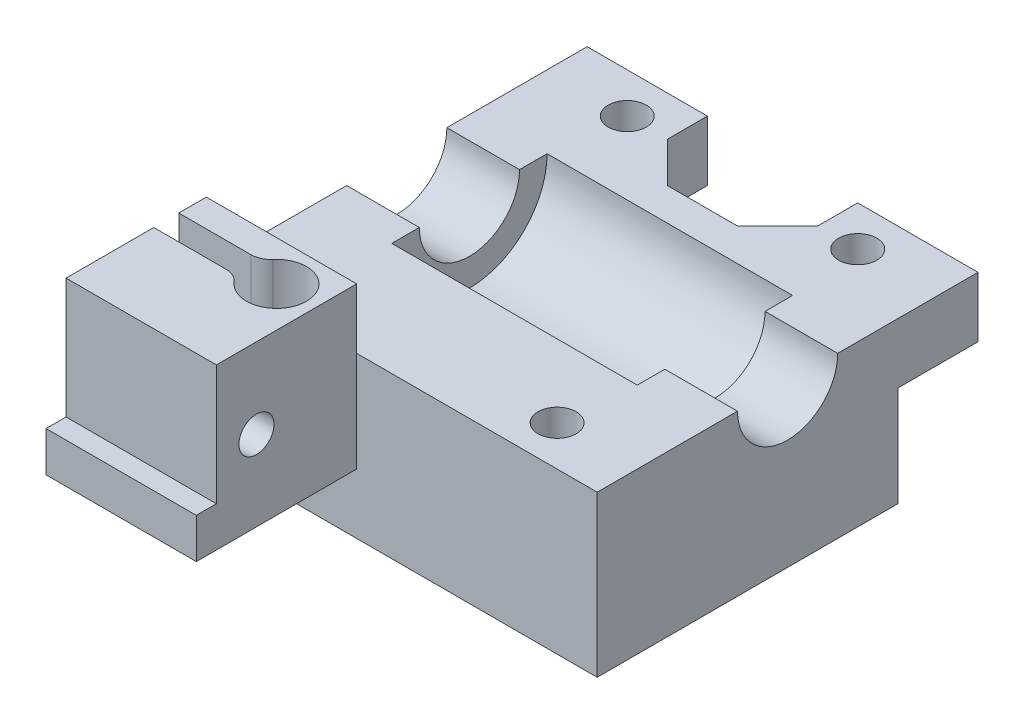
SolidWorks part; units mm, degrees
ref_plane "Front Plane" through (0, 0, 0) normal (0, 0, 1) x (1, 0, 0)
ref_plane "Top Plane" through (0, 0, 0) normal (0, 1, 0) x (1, 0, 0)
ref_plane "Right Plane" through (0, 0, 0) normal (1, 0, 0) x (0, 0, -1)
sketch "Sketch1" plane through (0, 0, 0) normal (0, 1, 0) x (1, 0, 0)
  line L1 (-15.5, 11) -> (15.5, 11)
  line L2 (-15.5, 11) -> (-15.5, -11)
  line L3 (-15.5, -11) -> (15.5, -11)
  line L4 (15.5, 11) -> (15.5, -11)
  line L5 (-15.5, 11) -> (15.5, -11) construction
  line L6 (-15.5, -11) -> (15.5, 11) construction
  point P0 (0, 0)
  dimension "D1" = 31
  dimension "D2" = 22
extrude "Boss-Extrude1" add sketch "Sketch1" along normal blind 11
sketch "Sketch2" plane through (0, 0, 0) normal (0, 1, 0) x (1, 0, 0)
  line L4 (15.5, -11) -> (15.5, 11)
  line L5 (-15.5, -11) -> (15.5, -11)
  line L6 (-15.5, 11) -> (-15.5, -11)
  line L7 (15.5, 11) -> (-15.5, 11)
  line L8 (15.5, -11) -> (15.5, 11)
  line L9 (-15.5, -11) -> (15.5, -11)
  line L10 (-15.5, 11) -> (-15.5, -11)
  line L11 (15.5, 11) -> (-15.5, 11)
  circle A0 centre (0, 0) radius 7.8438
  dimension "D1" = 0
extrude "Boss-Extrude2" add sketch "Sketch2" against normal blind 5
sketch "Sketch3" plane through (0, 11, 0) normal (0, 1, 0) x (1, 0, 0)
  line L1 (12.25, -7.75) -> (-12.25, -7.75)
  line L2 (12.25, -7.75) -> (12.25, 7.75)
  line L3 (12.25, 7.75) -> (-12.25, 7.75)
  line L4 (-12.25, -7.75) -> (-12.25, 7.75)
  line L5 (12.25, -7.75) -> (-12.25, 7.75) construction
  line L6 (12.25, 7.75) -> (-12.25, -7.75) construction
  point P0 (0, 0)
  dimension "D1" = 15.5
  dimension "D2" = 24.5
extrude "Cut-Extrude1" cut sketch "Sketch3" against normal blind 7.75
fillet "Fillet1" radius 7.75 2 edges at (0, 3.25, 7.75) (0, 3.25, -7.75)
sketch "Sketch4" plane through (-12.25, 0, 0) normal (1, 0, 0) x (0, 0, -1)
  line L0 (7.75, 11) -> (-7.75, 11) construction
  circle A0 centre (0, 11) radius 5
  dimension "D1" = 10
extrude "Cut-Extrude2" cut sketch "Sketch4" against normal through all both and the other way through all
sketch "Sketch5" plane through (0, 11, 0) normal (0, 1, 0) x (1, 0, 0)
  line L1 (15.5, -11) -> (7.5, -11)
  line L2 (15.5, -11) -> (15.5, -19)
  line L3 (15.5, -19) -> (7.5, -19)
  line L4 (7.5, -11) -> (7.5, -19)
  circle A0 centre (11.5, -15) radius 1.9058
  dimension "D1" = 8
  dimension "D2" = 8
  dimension "D3" = 4
  dimension "D4" = 4
extrude "Boss-Extrude3" add sketch "Sketch5" against normal blind 6
sketch "Sketch6" plane through (0, 5, 0) normal (0, -1, 0) x (1, 0, 0)
  line L4 (15.5, 11) -> (15.5, 19)
  line L5 (15.5, 19) -> (7.5, 19)
  line L6 (7.5, 19) -> (7.5, 11)
  line L7 (7.5, 11) -> (15.5, 11)
  line L8 (15.5, 11) -> (15.5, 19)
  line L9 (15.5, 19) -> (7.5, 19)
  line L10 (7.5, 19) -> (7.5, 11)
  line L11 (7.5, 11) -> (15.5, 11)
  circle A0 centre (11.5, 15) radius 1.9058 construction
  circle A1 centre (11.5, 15) radius 1.9058
  circle A2 centre (11.5, 15) radius 3
  circle M6 centre (11.5, 15) radius 1.9058
  dimension "D2" = 6
  dimension "D1" = 0
extrude "Cut-Extrude3" cut sketch "Sketch6" against normal blind 3 contours A2 M6 region at (8.5849, 5, 15)
mirror "Mirror8" about plane through (0, 0, 0) normal (1, 0, 0) of "Cut-Extrude3", "Boss-Extrude3"
mirror "Mirror9" about plane through (0, 0, 0) normal (0, 0, 1) of "Mirror8"
chamfer "Chamfer2" distance 4 angle 45 4 edges at (-7.5, 8, 11) (7.5, 8, 11) (-7.5, 8, -11) (7.5, 8, -11)
sketch "Sketch8" plane through (0, 11, 0) normal (0, 1, 0) x (1, 0, 0)
  line L0 (-15.5, -11) -> (15.5, -11) construction
  line L1 (-15.5, -11) -> (15.5, -11)
  line L3 (-15.5, -11) -> (15.5, -11)
  line L4 (-15.5, -11) -> (-15.5, -19)
  line L5 (-15.5, -19) -> (15.5, -19)
  line L6 (15.5, -11) -> (15.5, -19)
  circle A0 centre (-11.5, -15) radius 3 construction
  circle A1 centre (11.5, -15) radius 3 construction
  circle A2 centre (-11.5, -15) radius 3
  circle A3 centre (11.5, -15) radius 3
  line M6 (-15.5, -5) -> (-15.5, -19)
  line M7 (-15.5, -19) -> (-7.5, -19)
  line M8 (-7.5, -19) -> (-7.5, -15)
  line M9 (-7.5, -15) -> (-3.5, -11)
  line M10 (-3.5, -11) -> (3.5, -11)
  line M11 (3.5, -11) -> (7.5, -15)
  line M12 (7.5, -15) -> (7.5, -19)
  line M13 (7.5, -19) -> (15.5, -19)
  line M14 (15.5, -19) -> (15.5, -5)
extrude "Boss-Extrude4" add sketch "Sketch8" against normal up to surface (16 mm away) contours L5 M8 M12 M11 M10 M9 | L1 A3 M11 M12 M13 M14 | L1 A2 M6 M7 M8 M9 region at (-9.5, 11, 11.1442) region at (0, 11, 15.4103) region at (9.5, 11, 11.1442) up to face at (0, -5, 7.8438)
sketch "Sketch9" plane through (-15.5, 0, 0) normal (-1, 0, 0) x (0, 0, 1)
  line L0 (19, -5) -> (19, 11) construction
  line L1 (19, -5) -> (19, 11)
  line L3 (19, 1) -> (35, 1)
  line L4 (19, 1) -> (19, 17)
  line L5 (19, 17) -> (35, 17)
  line L6 (35, 1) -> (35, 17)
  circle A0 centre (29, 9) radius 1.75
  dimension "D3" = 3.5
  dimension "D1" = 16
  dimension "D2" = 6
  dimension "D4" = 8
  dimension "D5" = 16
  dimension "D6" = 10
extrude "Boss-Extrude5" add sketch "Sketch9" against normal blind 16 contours L3 L6 L5 L4 L1 A0 region at (-15.5, 9, 26.9219)
sketch "Sketch10" plane through (0, 17, 0) normal (0, 1, 0) x (1, 0, 0)
  line L1 (-8.5, -21.75) -> (-23.039, -21.75)
  line L2 (-8.5, -21.75) -> (-8.5, -24.25)
  line L3 (-8.5, -24.25) -> (-23.039, -24.25)
  line L4 (-15.5, -19) -> (-15.5, -35)
  line L5 (-15.5, -35) -> (0.5, -35)
  line L6 (0.5, -35) -> (0.5, -19)
  line L7 (0.5, -19) -> (-15.5, -19)
  line L8 (-15.5, -19) -> (-15.5, -35)
  line L9 (-15.5, -35) -> (0.5, -35)
  line L10 (0.5, -35) -> (0.5, -19)
  line L11 (0.5, -19) -> (-15.5, -19)
  line L12 (-23.039, -21.75) -> (-23.039, -24.25)
  circle A0 centre (-8.5, -23) radius 3
  line M7 (-15.5, -19) -> (-15.5, -35)
  dimension "D5" = 6
  dimension "D2" = 2.5
  dimension "D3" = 1.25
  dimension "D4" = 4
  dimension "D6" = 7
  dimension "D1" = 0
extrude "Cut-Extrude6" cut sketch "Sketch10" against normal blind 9 contours A0 L1 L3 M7 | L3 A0 L1 L2 | L1 A0 L3 L2 region at (-9.9565, 17, 23) region at (-7.9952, 17, 23) region at (-13.4546, 17, 23)
sketch "Sketch11" plane through (-15.5, 0, 0) normal (-1, 0, 0) x (0, 0, 1)
  line L1 (29, 12.1754) -> (26.25, 10.5877)
  line L2 (26.25, 10.5877) -> (26.25, 7.4123)
  line L3 (26.25, 7.4123) -> (29, 5.8246)
  line L4 (29, 5.8246) -> (31.75, 7.4123)
  line L5 (31.75, 7.4123) -> (31.75, 10.5877)
  line L6 (31.75, 10.5877) -> (29, 12.1754)
  circle A0 centre (29, 9) radius 1.75 construction
  circle A1 centre (29, 9) radius 1.75
  circle A2 centre (29, 9) radius 2.75 construction
  dimension "D1" = 5.5
extrude "Cut-Extrude7" cut sketch "Sketch11" against normal blind 8
fillet "Fillet2" radius 2 2 edges at (-11.2272, 12.5, 21.75) (-11.2272, 12.5, 24.25)
sketch "Sketch12" plane through (0, 8, 0) normal (0, 1, 0) x (1, 0, 0)
  arc A0 (-10.7798, -24.95) -> (-10.7798, -21.05) centre (-8.5, -23) ccw construction
  arc A1 (-10.7798, -24.95) -> (-10.7798, -21.05) centre (-8.5, -23) ccw
  circle A2 centre (-8.5, -23) radius 1.75
  dimension "D1" = 3.5
extrude "Cut-Extrude8" cut sketch "Sketch12" along normal through all both and the other way through all contours A2
sketch "Sketch13" plane through (0, 1, 0) normal (0, -1, 0) x (1, 0, 0)
  line L1 (-5.3246, 23) -> (-6.9123, 25.75)
  line L2 (-6.9123, 25.75) -> (-10.0877, 25.75)
  line L3 (-10.0877, 25.75) -> (-11.6754, 23)
  line L4 (-11.6754, 23) -> (-10.0877, 20.25)
  line L5 (-10.0877, 20.25) -> (-6.9123, 20.25)
  line L6 (-6.9123, 20.25) -> (-5.3246, 23)
  circle A0 centre (-8.5, 23) radius 1.75 construction
  circle A1 centre (-8.5, 23) radius 1.75
  circle A2 centre (-8.5, 23) radius 2.75 construction
  dimension "D1" = 5.5
extrude "Cut-Extrude9" cut sketch "Sketch13" against normal blind 3
sketch "Sketch15" plane through (-15.5, 0, 0) normal (-1, 0, 0) x (0, 0, 1)
  line L0 (29, 12.1754) -> (26.25, 10.5877) construction
  line L1 (31.75, 10.5877) -> (29, 12.1754) construction
  line L2 (31.75, 7.4123) -> (31.75, 10.5877) construction
  line L3 (29, 5.8246) -> (31.75, 7.4123) construction
  line L4 (26.25, 7.4123) -> (29, 5.8246) construction
  line L5 (26.25, 10.5877) -> (26.25, 7.4123) construction
  line L6 (29, 12.1754) -> (26.25, 10.5877)
  line L7 (31.75, 10.5877) -> (29, 12.1754)
  line L8 (31.75, 7.4123) -> (31.75, 10.5877)
  line L9 (29, 5.8246) -> (31.75, 7.4123)
  line L10 (26.25, 7.4123) -> (29, 5.8246)
  line L11 (26.25, 10.5877) -> (26.25, 7.4123)
  line L15 (24.25, 17) -> (24.25, 8)
  line L16 (24.25, 8) -> (21.75, 8)
  line L17 (21.75, 8) -> (21.75, 17)
  line L18 (21.75, 17) -> (19, 17)
  line L19 (19, 17) -> (19, 11)
  line L20 (19, 11) -> (5, 11)
  line L21 (-5, 11) -> (-19, 11)
  line L22 (-19, 11) -> (-19, 5)
  line L23 (-19, 5) -> (-11, 5)
  line L24 (-11, 5) -> (-11, -5)
  line L25 (-11, -5) -> (19, -5)
  line L26 (19, -5) -> (19, 1)
  line L27 (19, 1) -> (35, 1)
  line L28 (35, 1) -> (35, 17)
  line L29 (35, 17) -> (24.25, 17)
  line L30 (24.25, 17) -> (24.25, 8)
  line L31 (24.25, 8) -> (21.75, 8)
  line L32 (21.75, 8) -> (21.75, 17)
  line L33 (21.75, 17) -> (19, 17)
  line L34 (19, 17) -> (19, 11)
  line L35 (19, 11) -> (5, 11)
  line L36 (-5, 11) -> (-19, 11)
  line L37 (-19, 11) -> (-19, 5)
  line L38 (-19, 5) -> (-11, 5)
  line L39 (-11, 5) -> (-11, -5)
  line L40 (-11, -5) -> (19, -5)
  line L41 (19, -5) -> (19, 1)
  line L42 (19, 1) -> (35, 1)
  line L43 (35, 1) -> (35, 17)
  line L44 (35, 17) -> (24.25, 17)
  arc A1 (-5, 11) -> (5, 11) centre (0, 11) ccw
  arc A2 (-5, 11) -> (5, 11) centre (0, 11) ccw
  dimension "D1" = 0
extrude "Boss-Extrude8" add sketch "Sketch15" along normal blind 4
sketch "Sketch17" plane through (15.5, 0, 0) normal (1, 0, 0) x (0, 0, -1)
  line L7 (-5, 11) -> (-19, 11)
  line L8 (-19, 11) -> (-19, -5)
  line L9 (-19, -5) -> (11, -5)
  line L10 (11, -5) -> (11, 5)
  line L11 (11, 5) -> (19, 5)
  line L12 (19, 5) -> (19, 11)
  line L13 (19, 11) -> (5, 11)
  line L14 (-5, 11) -> (-19, 11)
  line L15 (-19, 11) -> (-19, -5)
  line L16 (-19, -5) -> (11, -5)
  line L17 (11, -5) -> (11, 5)
  line L18 (11, 5) -> (19, 5)
  line L19 (19, 5) -> (19, 11)
  line L20 (19, 11) -> (5, 11)
  arc A1 (-5, 11) -> (5, 11) centre (0, 11) ccw
  arc A2 (-5, 11) -> (5, 11) centre (0, 11) ccw
  dimension "D1" = 0
extrude "Boss-Extrude9" add sketch "Sketch17" along normal blind 4
sketch "Sketch18" plane through (0.5, 0, 0) normal (1, 0, 0) x (0, 0, -1)
  line L5 (-35, 1) -> (-19, 1)
  line L6 (-19, 1) -> (-19, 11)
  line L7 (-19, 11) -> (-19, 17)
  line L8 (-19, 17) -> (-35, 17)
  line L9 (-35, 17) -> (-35, 1)
  line L10 (-35, 1) -> (-19, 1)
  line L11 (-19, 1) -> (-19, 11)
  line L12 (-19, 11) -> (-19, 17)
  line L13 (-19, 17) -> (-35, 17)
  line L14 (-35, 17) -> (-35, 1)
  circle A0 centre (-29, 9) radius 1.75 construction
  circle A1 centre (-29, 9) radius 1.75
  dimension "D1" = 0
extrude "Cut-Extrude11" cut sketch "Sketch18" against normal blind 5
sketch "Sketch20" plane through (0, 17, 0) normal (0, 1, 0) x (1, 0, 0)
  line L0 (-19.5, -35) -> (-19.5, -24.25) construction
  line L1 (-4.5, -35) -> (-19.5, -35)
  line L2 (-4.5, -35) -> (-4.5, -33)
  line L3 (-4.5, -33) -> (-19.5, -33)
  line L4 (-19.5, -35) -> (-19.5, -33)
  dimension "D1" = 2
extrude "Cut-Extrude12" cut sketch "Sketch20" against normal blind 12
ref_plane "Plane1" through (0, 0, 27) normal (0, 0, 1) x (1, 0, 0)
